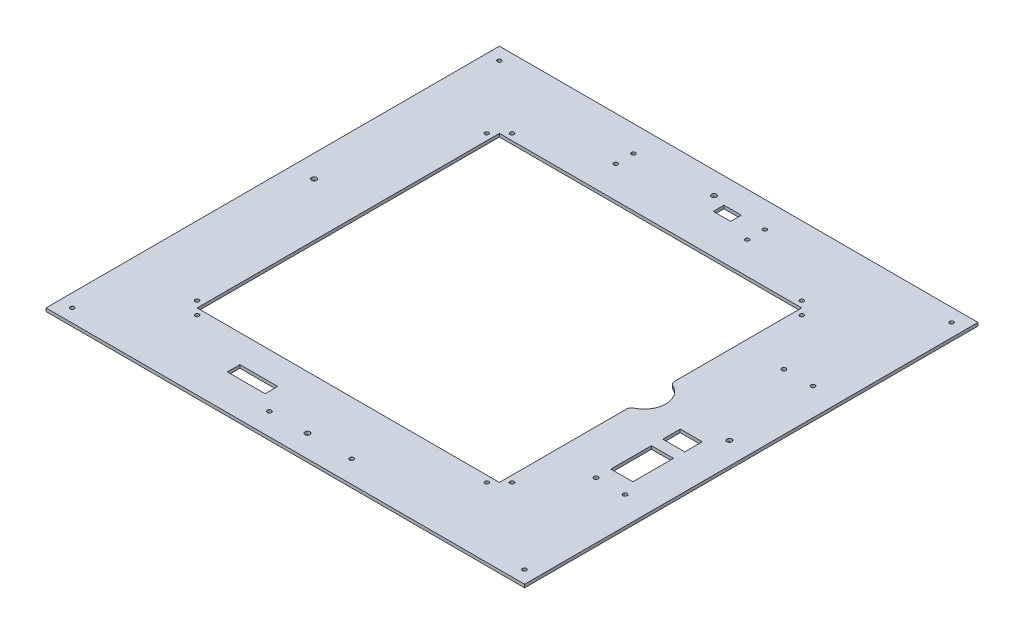
SolidWorks part; units mm, degrees
ref_plane "Front" through (0, 0, 0) normal (0, 0, 1) x (1, 0, 0)
ref_plane "Top" through (0, 0, 0) normal (0, 1, 0) x (1, 0, 0)
ref_plane "Right" through (0, 0, 0) normal (1, 0, 0) x (0, 0, -1)
sketch "Sketch1" plane through (0, 0, 0) normal (0, 1, 0) x (1, 0, 0)
  line L0 (-55, 0) -> (55, 0) construction
  line L1 (-242.5515, 228.6) -> (240.0485, 228.6)
  line L2 (-242.5515, 228.6) -> (-242.5515, -228.6)
  line L3 (-242.5515, -228.6) -> (240.0485, -228.6)
  line L4 (240.0485, 228.6) -> (240.0485, -228.6)
  line L5 (-242.5515, 228.6) -> (240.0485, -228.6) construction
  line L6 (-242.5515, -228.6) -> (240.0485, 228.6) construction
  line L7 (-166.3515, 152.4) -> (138.4485, 152.4)
  line L8 (-166.3515, 152.4) -> (-166.3515, -152.4)
  line L9 (-166.3515, -152.4) -> (138.4485, -152.4)
  line L11 (-166.3515, 152.4) -> (138.4485, -152.4) construction
  line L12 (-166.3515, -152.4) -> (138.4485, 152.4) construction
  line L13 (-160.0015, 146.05) -> (132.0985, 146.05)
  line L14 (-160.0015, 146.05) -> (-160.0015, -146.05)
  line L15 (-160.0015, -146.05) -> (132.0985, -146.05)
  line L16 (132.0985, 146.05) -> (132.0985, -146.05)
  line L17 (-160.0015, 146.05) -> (132.0985, -146.05) construction
  line L18 (-160.0015, -146.05) -> (132.0985, 146.05) construction
  line L19 (-166.3515, -152.4) -> (-140.9515, -152.4)
  line L23 (-242.5515, 0) -> (240.0485, 0) construction
  line L28 (182.9854, -43.6118) -> (205.1825, -43.6118)
  line L29 (182.9854, -43.6118) -> (182.9854, -84.5553)
  line L30 (182.9854, -84.5553) -> (205.1825, -84.5553)
  line L31 (205.1825, -43.6118) -> (205.1825, -84.5553)
  line L32 (182.9854, -32.247) -> (205.1825, -32.247)
  line L33 (182.9854, -32.247) -> (182.9854, -14.612)
  line L34 (182.9854, -14.612) -> (205.1825, -14.612)
  line L35 (205.1825, -32.247) -> (205.1825, -14.612)
  line L40 (27.0379, 202.954) -> (9.5991, 202.954)
  line L41 (27.0379, 202.954) -> (27.0379, 192.0704)
  line L42 (27.0379, 192.0704) -> (9.5991, 192.0704)
  line L43 (9.5991, 202.954) -> (9.5991, 192.0704)
  line L44 (-95.2315, -180.3456) -> (-57.1315, -180.3456)
  line L45 (-95.2315, -180.3456) -> (-95.2315, -193.0456)
  line L46 (-95.2315, -193.0456) -> (-57.1315, -193.0456)
  line L47 (-57.1315, -180.3456) -> (-57.1315, -193.0456)
  line L50 (138.4485, -20.7413) -> (138.4485, -152.4)
  line L51 (138.4485, 20.7413) -> (138.4485, 152.4)
  circle A0 centre (51.3519, 202.311) radius 2
  circle A1 centre (51.3519, 184.531) radius 2
  circle A2 centre (-81.1091, 202.311) radius 2
  circle A3 centre (-81.1091, 184.531) radius 2
  circle A4 centre (212.3904, -99.5798) radius 2.0955
  circle A5 centre (212.3904, 89.828) radius 2.0955
  circle A6 centre (-39.6436, -206.2861) radius 2.1
  circle A7 centre (43.3382, -206.2861) radius 2.1
  circle A8 centre (-172.7335, 146.082) radius 2
  circle A9 centre (-160.0335, 158.782) radius 2
  circle A12 centre (-160.0335, -158.782) radius 2
  circle A13 centre (-172.7335, -146.082) radius 2
  circle A14 centre (132.1305, 158.782) radius 2
  circle A15 centre (144.8305, 146.082) radius 2
  circle A16 centre (144.8305, -146.082) radius 2
  circle A17 centre (132.1305, -158.782) radius 2
  circle A18 centre (-229.8327, 215.8812) radius 2
  circle A19 centre (226.7201, 215.2716) radius 2
  circle A20 centre (-229.3755, -215.2716) radius 2
  circle A21 centre (227.2281, -215.9066) radius 2
  circle A22 centre (-220.0871, 19.264) radius 2.54
  circle A23 centre (-1.2915, -206.2372) radius 2.54
  circle A24 centre (-3.8315, 206.2626) radius 2.54
  circle A25 centre (217.7111, 0.294) radius 2.54
  circle A26 centre (182.9854, -99.5798) radius 2.159
  circle A28 centre (182.9854, 89.828) radius 2.159
  arc A31 (138.4485, 20.7413) -> (138.4485, -20.7413) centre (132.0985, 0) cw
  point P0 (-1.2515, 0)
  point P6 (-44.5662, -1.1741)
  point P11 (-84.1987, 3.6789)
  point P21 (-13.9515, 0)
  point P22 (-13.9515, 0)
  point P23 (-1.2515, 0)
  dimension "D15" = 4
  dimension "D16" = 4
  dimension "D17" = 26.289
  dimension "D18" = 17.78
  dimension "D19" = 188.6966
  dimension "D20" = 132.461
  dimension "D22" = 27.6581
  dimension "D23" = 4.191
  dimension "D24" = 129.0202
  dimension "D26" = 4.2
  dimension "D27" = 22.3139
  dimension "D28" = 202.9079
  dimension "D29" = 82.9818
  dimension "D33" = 69.818
  dimension "D34" = 82.518
  dimension "D35" = 4
  dimension "D36" = 69.818
  dimension "D37" = 82.518
  dimension "D38" = 4
  dimension "D39" = 107.918
  dimension "D40" = 69.818
  dimension "D41" = 95.218
  dimension "D42" = 82.518
  dimension "D43" = 95.218
  dimension "D44" = 82.518
  dimension "D45" = 69.818
  dimension "D46" = 107.918
  dimension "D47" = 4
  dimension "D48" = 4
  dimension "D49" = 4
  dimension "D50" = 4
  dimension "D51" = 12.7188
  dimension "D53" = 13.3284
  dimension "D54" = 13.3284
  dimension "D55" = 13.176
  dimension "D56" = 13.3284
  dimension "D57" = 4
  dimension "D58" = 4
  dimension "D59" = 4
  dimension "D60" = 12.8204
  dimension "D61" = 4
  dimension "D62" = 12.6934
  dimension "D63" = 22.4644
  dimension "D64" = 247.864
  dimension "D65" = 22.3628
  dimension "D66" = 241.26
  dimension "D67" = 5.08
  dimension "D68" = 5.08
  dimension "D69" = 5.08
  dimension "D70" = 22.3374
  dimension "D71" = 238.72
  dimension "D72" = 22.3374
  dimension "D73" = 228.306
  dimension "D74" = 5.08
  dimension "D1" = 457.2
  dimension "D2" = 482.6
  dimension "D3" = 304.8
  dimension "D4" = 304.8
  dimension "D5" = 76.2
  dimension "D6" = 292.1
  dimension "D7" = 146.05
  dimension "D8" = 228.6
  dimension "D21" = 17.78
  dimension "D25" = 189.4078
  dimension "D30" = 12.7
  dimension "D31" = 185.42
  dimension "D32" = 38.1
  dimension "D52" = 12.7188
extrude "Boss-Extrude1" add sketch "Sketch1" along normal blind 3.175 contours L4 L1 L2 L3 L7 L9 L8 region at (-1.2515, 0, -221.9522)
fillet "Fillet2" radius 5 2 edges at (138.4485, 1.5875, 20.7413) (138.4485, 1.5875, -20.7413)
